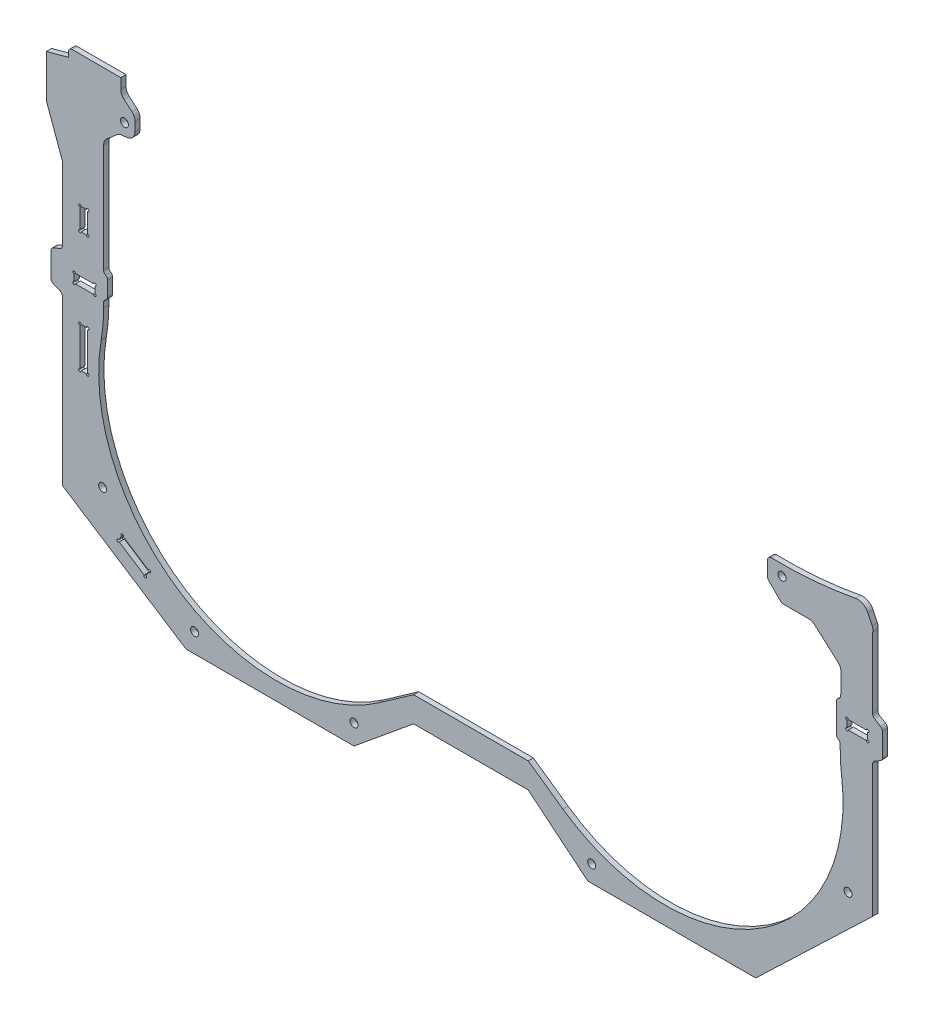
SolidWorks part; units mm, degrees
material "PPS"
ref_plane "前视基准面" through (0, 0, 0) normal (0, 0, 1) x (1, 0, 0)
ref_plane "上视基准面" through (0, 0, 0) normal (0, 1, 0) x (1, 0, 0)
ref_plane "右视基准面" through (0, 0, 0) normal (1, 0, 0) x (0, 0, -1)
sketch "草图1" plane through (0, 0, 0) normal (0, 0, 1) x (1, 0, 0)
  line L0 (-816.4831, 0) -> (39952.7477, 0) construction
  line L1 (0, 10.8762) -> (0, -592.6628) construction
  line L2 (0, 0) -> (206.9686, -284.8678) construction
  line L9 (155.1848, -135.6229) -> (110.024, -178.8146)
  line L10 (110.024, -178.8146) -> (45.146, -178.8146)
  line L60 (-110.024, -178.8146) -> (-45.146, -178.8146)
  line L119 (-135.8935, -19.3983) -> (-141.8504, -24.5203)
  line L187 (152.75, -77.5) -> (145.75, -77.5) construction
  line L188 (152.75, -77.5) -> (152.75, -75) construction
  line L189 (145.75, -77.5) -> (145.75, -75) construction
  line L190 (152.75, -75) -> (145.75, -75) construction
  line L191 (-145.75, -75) -> (-152.75, -75) construction
  line L192 (-152.75, -75) -> (-152.75, -77.5) construction
  line L193 (-152.75, -77.5) -> (-145.75, -77.5) construction
  line L194 (-145.75, -77.5) -> (-145.75, -75) construction
  line L195 (145.25, -74.5) -> (153.25, -74.5)
  line L196 (153.25, -74.5) -> (153.25, -78)
  line L197 (153.25, -78) -> (145.25, -78)
  line L198 (145.25, -78) -> (145.25, -74.5)
  line L199 (-153.25, -78) -> (-145.25, -78)
  line L200 (-153.25, -74.5) -> (-153.25, -78)
  line L201 (-145.25, -74.5) -> (-153.25, -74.5)
  line L202 (-145.25, -78) -> (-145.25, -74.5)
  line L203 (114.5778, -42.9165) -> (114.5778, -35.185)
  line L204 (-135.1929, -0.25) -> (-155.5041, -0.25)
  line L205 (155.0114, -38.4796) -> (153.3418, -34.9767)
  line L206 (-155.5041, -0.25) -> (-155.5041, -3.6009)
  line L207 (-155.5041, -3.6009) -> (-163.9299, -5.8429)
  line L208 (-155.5041, -3.6009) -> (-170.0041, -7.4592) construction
  line L209 (-163.9299, -5.8429) -> (-163.9299, -22.4613)
  line L210 (-163.9299, -22.4613) -> (-157.7253, -39.5836)
  line L211 (-157.7253, -39.5836) -> (-157.7253, -148.0115)
  line L212 (-157.7253, -148.0115) -> (-110.024, -178.8146)
  line L215 (114.5778, -32.685) -> (114.5778, -42.9165) construction
  line L216 (120.0778, -48.4165) -> (131.782, -48.4165)
  line L217 (131.782, -48.4165) -> (142.9662, -58.3127)
  line L219 (151.7709, -31.6811) -> (155.0114, -38.4796) construction
  line L220 (155.1848, -40.6053) -> (155.1848, -135.6229)
  line L221 (120.1823, -39.335) -> (149.4323, -39.335) construction
  line L222 (92.9352, -48.4165) -> (142.5788, -48.4165) construction
  line L223 (75, -103.2286) -> (164.6276, -103.2286) construction
  line L224 (75, -103.2286) -> (35.5666, -159.5453) construction
  line L226 (35.5666, -159.5453) -> (22.126, -150.1341)
  line L227 (22.126, -150.1341) -> (-22.126, -150.1341)
  line L228 (22.126, -159.8702) -> (-22.126, -159.8702)
  line L229 (22.126, -159.8702) -> (45.146, -178.8146)
  line L230 (-35.5666, -159.5453) -> (-22.126, -150.1341)
  line L231 (-22.126, -159.8702) -> (-45.146, -178.8146)
  line L233 (114.5778, -42.9165) -> (120.0778, -48.4165)
  line L234 (75, -103.2286) -> (142.5988, -90.7) construction
  line L235 (142.9662, -58.3127) -> (142.5988, -90.7)
  line L236 (142.5988, -90.7) -> (142.5988, -57.1472) construction
  line L238 (-141.8504, -87.1793) -> (-75, -103.2286) construction
  line L239 (-75, -103.2286) -> (-143.75, -103.2286) construction
  line L240 (-141.8504, -24.5203) -> (-141.8504, -87.1793)
  line L241 (-135.1929, -0.25) -> (-135.1929, -5.85)
  line L242 (-135.1929, -5.85) -> (-129.7197, -10.5767)
  line L243 (-129.7197, -10.5767) -> (-129.7197, -18.7984)
  line L244 (-129.7197, -18.7984) -> (-135.8935, -19.3983)
  circle A76 centre (75, -103.2286) radius 68.75 construction
  circle A78 centre (-133.8062, -14.6009) radius 1.55
  arc A79 (155.0114, -38.4796) -> (155.1848, -40.6053) centre (152.3033, -39.7704) cw
  circle A80 centre (-75, -103.2286) radius 68.75 construction
  arc A81 (148.5011, -30.0249) -> (151.7709, -31.6811) centre (149.0628, -32.9719) cw construction
  arc A82 (153.902, -42.309) -> (155.0114, -38.4796) centre (152.3033, -39.7704) ccw construction
  arc A83 (148.5011, -30.0249) -> (114.5778, -32.685) centre (119.5082, 122.0773) cw construction
  arc A84 (97.7907, -31.2329) -> (148.5011, -30.0249) centre (119.5082, 122.0773) ccw construction
  circle A85 centre (149.4323, -39.335) radius 1.55 construction
  circle A86 centre (120.1823, -39.335) radius 1.55
  arc A87 (35.5666, -159.5453) -> (143.75, -103.2286) centre (75, -103.2286) ccw
  arc A88 (-35.5666, -159.5453) -> (-143.75, -103.2286) centre (-75, -103.2286) cw
  arc A89 (142.5988, -90.7) -> (143.75, -103.2286) centre (75, -103.2286) cw
  arc A91 (-143.75, -103.2286) -> (-141.8504, -87.1793) centre (-75, -103.2286) cw
  arc A92 (148.5011, -32.5249) -> (114.5778, -35.185) centre (119.5082, 119.5773) cw
  arc A93 (148.5011, -32.5249) -> (153.3418, -34.9767) centre (149.3327, -36.8876) cw
  point P10 (149.25, -75)
  point P29 (0, -150.1341)
  point P38 (153.25, -76.25)
  point P92 (0, -159.8702)
  dimension "D1" = 36
  dimension "D2" = 75
  dimension "D3" = 137.5
  dimension "D6" = 75
  dimension "D7" = 149.25
  dimension "D15" = 125
  dimension "D14" = 3.1
  dimension "D4" = 2.5
  dimension "D5" = 7
  dimension "D8" = 7
  dimension "D9" = 0.5
  dimension "D10" = 0.5
  dimension "D11" = 0.5
  dimension "D12" = 0.5
  dimension "D13" = 29.25
  dimension "D16" = 10.5
  dimension "D17" = 0.65
  dimension "D18" = 13.5
  dimension "D19" = 0.25
  dimension "D20" = 114.5778
  dimension "D21" = 2.5
extrude "凸台-拉伸1" add sketch "草图1" along normal blind 2
sketch "草图2" plane through (0, 0, 0) normal (0, 0, 1) x (1, 0, 0)
  line L0 (155.1848, -68.75) -> (158.9348, -70.9151)
  line L1 (155.1848, -135.6229) -> (155.1848, -40.6053) construction
  line L2 (158.9348, -70.9151) -> (158.9348, -81.5849)
  line L3 (158.9348, -81.5849) -> (155.1848, -83.75)
  line L4 (155.1848, -83.75) -> (155.1848, -68.75)
  line L5 (153.25, -76.25) -> (184.2947, -76.25) construction
  line L6 (153.25, -78) -> (153.25, -74.5) construction
  line L7 (-153.25, -76.25) -> (-171.2105, -76.25) construction
  line L8 (-153.25, -74.5) -> (-153.25, -78) construction
  line L9 (-157.7253, -68.75) -> (-157.7253, -83.75)
  line L10 (-157.7253, -39.5836) -> (-157.7253, -148.0115) construction
  line L11 (-157.7253, -83.75) -> (-162.2253, -81.886)
  line L12 (-162.2253, -81.886) -> (-162.2253, -70.614)
  line L13 (-162.2253, -70.614) -> (-157.7253, -68.75)
  line L14 (142.679, -83.6318) -> (141.179, -82.5815)
  line L15 (142.9662, -58.3127) -> (142.5988, -90.7) construction
  line L16 (141.179, -82.5815) -> (141.179, -69.9185)
  line L18 (142.679, -68.8682) -> (141.179, -69.9185)
  line L20 (142.8478, -68.75) -> (142.679, -83.6318)
  line L21 (142.8478, -68.75) -> (142.679, -68.8682)
  line L22 (-141.8504, -78.0009) -> (-140.3504, -76.9506)
  line L23 (-141.8504, -87.1793) -> (-141.8504, -24.5203) construction
  line L24 (-140.3504, -76.9506) -> (-140.3504, -69.8003)
  line L25 (-140.3504, -69.8003) -> (-141.8504, -68.75)
  line L27 (-145.25, -78) -> (-141.8504, -78.0009) construction
  line L28 (-141.8504, -68.75) -> (-141.8504, -78.0009)
  point P26 (141.179, -76.25)
  dimension "D1" = 3.75
  dimension "D2" = 7.5
  dimension "D3" = 60
  dimension "D4" = 67.5
  dimension "D5" = 4.5
  dimension "D6" = 1.5
  dimension "D7" = 125
  dimension "D8" = 125
  dimension "D9" = 125
  dimension "D10" = 1.5
extrude "凸台-拉伸2" add sketch "草图2" against normal up to surface from surface up to face at (-132.2562, -14.6009, 0) starting at face at (149.25, -76.25, 2)
fillet "圆角1" radius 66.25 2 edges at (-141.8504, -87.1793, 1) (142.5988, -90.7, 1)
fillet "圆角4" radius 1.5 20 edges at (155.1848, -68.75, 1) (158.9348, -70.9151, 1) (155.1848, -83.75, 1) (158.9348, -81.5849, 1) (-155.5041, -0.25, 1) (-157.7253, -68.75, 1) (-162.2253, -70.614, 1) (-162.2253, -81.886, 1) (-157.7253, -83.75, 1) (142.679, -83.6318, 1) (142.8478, -68.75, 1) (141.179, -69.9185, 1) (141.179, -82.5815, 1) (-141.8504, -68.75, 1) (-140.3504, -69.8003, 1) (-140.3504, -76.9506, 1) (-141.8504, -78.0009, 1) (120.0778, -48.4165, 1) (114.5778, -42.9165, 1) (114.5778, -35.185, 1)
sketch "板状设备接口" plane through (0, 0, 2) normal (0, 0, 1) x (1, 0, 0)
  line L0 (-151, -90.5) -> (-148, -90.5)
  line L1 (-148, -90.5) -> (-148, -106)
  line L2 (-148, -106) -> (-151, -106)
  line L3 (-151, -106) -> (-151, -90.5)
  line L5 (-151, -75) -> (-151, -77.5) construction
  line L6 (-151, -51) -> (-148, -51)
  line L7 (-148, -51) -> (-148, -59.5)
  line L8 (-148, -59.5) -> (-151, -59.5)
  line L9 (-151, -59.5) -> (-151, -51)
  line L10 (-145.25, -74.5) -> (-153.25, -74.5) construction
  line L11 (-153.25, -78) -> (-145.25, -78) construction
  line L12 (-134.6497, -153.092) -> (-124.1488, -159.8729)
  line L13 (-124.1488, -159.8729) -> (-125.7762, -162.3931)
  line L14 (-125.7762, -162.3931) -> (-136.2771, -155.6122)
  line L15 (-136.2771, -155.6122) -> (-134.6497, -153.092)
  line L21 (-157.7253, -148.0115) -> (-110.024, -178.8146) construction
  line L22 (-131.0266, -159.0026) -> (-133.8746, -163.413) construction
  dimension "D1" = 15
  dimension "D2" = 8.5
  dimension "D3" = 12.5
  dimension "D4" = 15.5
  dimension "D5" = 5.25
  dimension "D6" = 12.5
  dimension "D7" = 3
  dimension "D8" = 148
extrude "设备接口" cut sketch "板状设备接口" against normal through all
sketch "草图4" plane through (0, 0, 0) normal (0, 0, 1) x (1, 0, 0)
  line L0 (-157.7253, -84.7523) -> (-157.7253, -148.0115) construction
  line L1 (-110.024, -178.8146) -> (-45.146, -178.8146) construction
  line L2 (155.1848, -135.6229) -> (155.1848, -84.616) construction
  line L3 (-45.146, -171.0646) -> (-45.146, -178.8146) construction
  line L4 (45.146, -178.8146) -> (110.024, -178.8146) construction
  circle A0 centre (-142.2253, -140.8215) radius 1.55
  circle A1 centre (-45.146, -171.0646) radius 1.55
  circle A2 centre (-106.713, -171.3146) radius 1.55
  circle A3 centre (46.656, -172.3146) radius 1.55
  circle A4 centre (145.6848, -132.301) radius 1.55
  dimension "D5" = 3.1
  dimension "D1" = 15.5
  dimension "D2" = 7.5
  dimension "D3" = 7.75
  dimension "D4" = 9.5
  dimension "D6" = 6.5
extrude "切除-拉伸3" cut sketch "草图4" along normal through all
fillet "圆角5" radius 3.5 7 edges at (131.782, -48.4165, 1) (-141.8504, -24.5203, 1) (-129.7197, -10.5767, 1) (-135.1929, -5.85, 1) (-135.8935, -19.3983, 1) (-129.7197, -18.7984, 1) (142.9662, -58.3127, 1)
sketch "过切除" plane through (0, 0, 0) normal (0, 0, 1) x (1, 0, 0)
  circle A0 centre (-151, -51) radius 0.5
  circle A1 centre (-148, -51) radius 0.5
  circle A2 centre (-151, -59.5) radius 0.5
  circle A3 centre (-148, -59.5) radius 0.5
  circle A4 centre (-153.25, -74.5) radius 0.5
  circle A5 centre (-145.25, -74.5) radius 0.5
  circle A6 centre (-145.25, -78) radius 0.5
  circle A7 centre (-153.25, -78) radius 0.5
  circle A8 centre (-151, -90.5) radius 0.5
  circle A9 centre (-148, -90.5) radius 0.5
  circle A10 centre (-151, -106) radius 0.5
  circle A11 centre (-148, -106) radius 0.5
  circle A12 centre (-134.6497, -153.092) radius 0.5
  circle A13 centre (-136.2771, -155.6122) radius 0.5
  circle A14 centre (-124.1488, -159.8729) radius 0.5
  circle A15 centre (-125.7762, -162.3931) radius 0.5
  circle A16 centre (145.25, -74.5) radius 0.5
  circle A17 centre (153.25, -74.5) radius 0.5
  circle A18 centre (153.25, -78) radius 0.5
  circle A19 centre (145.25, -78) radius 0.5
  dimension "D1" = 1
extrude "这个是因为刀的限制不能切直角" cut sketch "过切除" along normal through all
sketch "草图7" plane through (0, 0, 2) normal (0, 0, 1) x (1, 0, 0)
  text T0 "这里板状设备的接口得和防撞圈固定板对齐\r\n"
